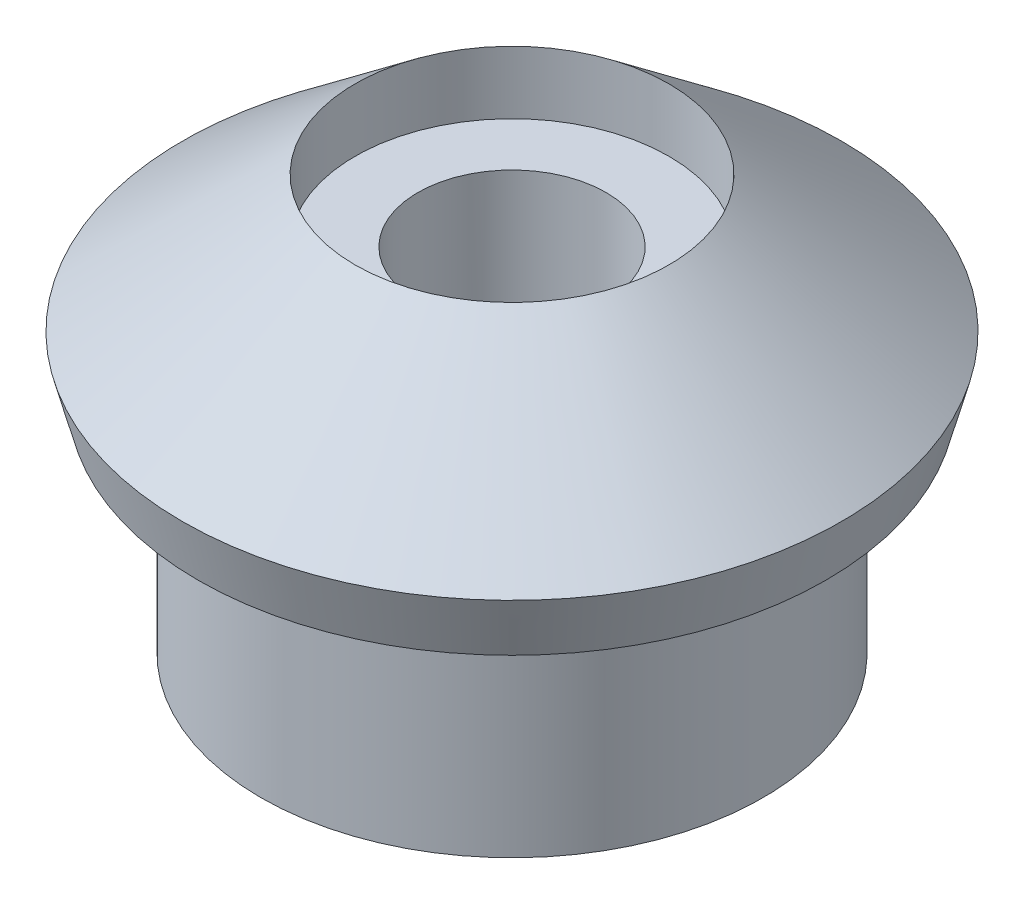
SolidWorks part; units mm, degrees
material "普通碳钢"
ref_plane "前视基准面" through (0, 0, 0) normal (0, 0, 1) x (1, 0, 0)
ref_plane "上视基准面" through (0, 0, 0) normal (0, 1, 0) x (1, 0, 0)
ref_plane "右视基准面" through (0, 0, 0) normal (1, 0, 0) x (0, 0, -1)
sketch "草图1" plane through (0, 0, 0) normal (1, 0, 0) x (0, 0, -1)
  line L0 (0, 56.9417) -> (0, 0) construction
  line L1 (0, 0) -> (58.8397, 0) construction
  line L2 (0, 11.2) -> (5, 11.2)
  line L3 (5, 11.2) -> (5, 13.2)
  line L4 (5, 13.2) -> (10.5, 8.8699)
  line L5 (10.5, 8.8699) -> (10, 7)
  line L6 (8, 7) -> (8, 0)
  line L7 (8, 0) -> (0, 0)
  line L8 (0, 0) -> (0, 11.2)
  line L9 (10, 7) -> (8, 7)
  dimension "D1" = 10.5
  dimension "D2" = 7
  dimension "D3" = 10
  dimension "D4" = 13.2
  dimension "D5" = 7
  dimension "D6" = 5
  dimension "D7" = 8
  dimension "D9" = 2
revolve "旋转1" add sketch "草图1" angle 360 about L0
sketch "草图2" plane through (0, 0, 0) normal (0, -1, 0) x (1, 0, 0)
  circle A0 centre (0, 0) radius 3
  dimension "D1" = 6
extrude "切除-拉伸1" cut sketch "草图2" against normal through all
sketch "草图3" plane through (0, 0, 0) normal (1, 0, 0) x (0, 0, -1)
  line L0 (-8, 0) -> (8, 0) construction
  circle A0 centre (0, 3) radius 1.5
  dimension "D1" = 3
  dimension "D2" = 3
extrude "切除-拉伸2" cut sketch "草图3" against normal through all
